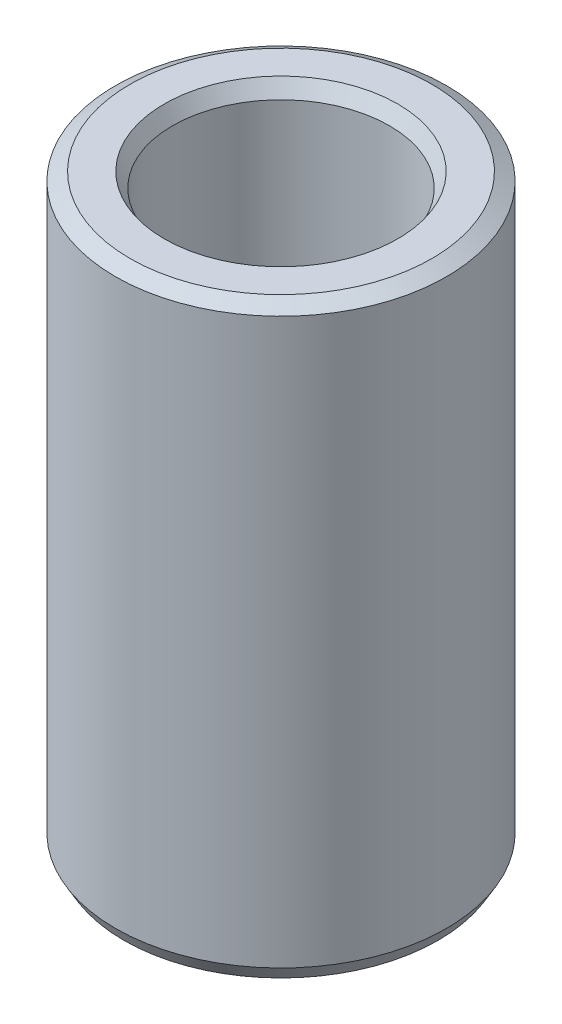
SolidWorks part; units mm, degrees
ref_plane "Front Plane" through (0, 0, 0) normal (0, 0, 1) x (1, 0, 0)
ref_plane "Top Plane" through (0, 0, 0) normal (0, 1, 0) x (1, 0, 0)
ref_plane "Right Plane" through (0, 0, 0) normal (1, 0, 0) x (0, 0, -1)
sketch "Sketch1" plane through (0, 0, 0) normal (0, 1, 0) x (1, 0, 0)
  circle A0 centre (0, 0) radius 40
  dimension "SLEEVE_OD" = 80
extrude "Boss-Extrude1" add sketch "Sketch1" along normal blind 141.9438
sketch "Sketch2" plane through (0, 0, 0) normal (0, 1, 0) x (1, 0, 0)
  circle A0 centre (0, 0) radius 26.1905
  dimension "BORE_D" = 52.3809
extrude "Cut-Extrude1" cut sketch "Sketch2" along normal through all
chamfer "Chamfer1" distance 2.0357 angle 60 4 edges at (0, 141.9438, 26.1905) (0, 0, 26.1905) (0, 0, 40) (0, 141.9438, 40) first distance on face at (0, 141.9438, 26.1905) first distance on face at (0, 0, 26.1905) first distance on face at (0, 141.9438, 40)
